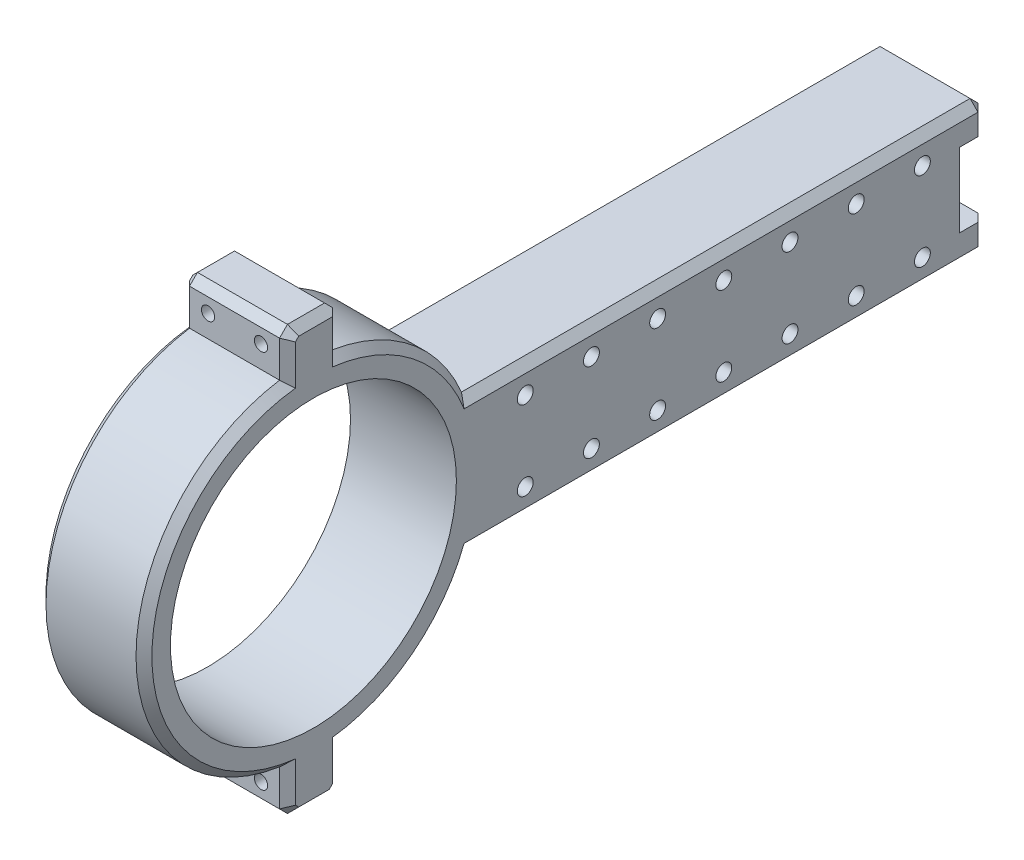
SolidWorks part; units mm, degrees
ref_plane "前视基准面" through (0, 0, 0) normal (0, 0, 1) x (1, 0, 0)
ref_plane "上视基准面" through (0, 0, 0) normal (0, 1, 0) x (1, 0, 0)
ref_plane "右视基准面" through (0, 0, 0) normal (1, 0, 0) x (0, 0, -1)
sketch "草图2" plane through (0, 0, 0) normal (1, 0, 0) x (0, 0, -1)
  circle A0 centre (0, 0) radius 32
  dimension "D1" = 64
extrude "凸台-拉伸1" add sketch "草图2" along normal blind 20
sketch "草图3" plane through (20, 0, 0) normal (1, 0, 0) x (0, 0, -1)
  circle A0 centre (0, 0) radius 27
  dimension "D1" = 54
extrude "切除-拉伸1" cut sketch "草图3" against normal through all
sketch "草图4" plane through (20, 0, 0) normal (1, 0, 0) x (0, 0, -1)
  line L1 (23.9322, 12.5) -> (122, 12.5)
  line L2 (23.9322, 12.5) -> (23.9322, -12.5)
  line L3 (23.9322, -12.5) -> (122, -12.5)
  line L4 (122, 12.5) -> (122, -12.5)
  line L5 (23.9322, 12.5) -> (122, -12.5) construction
  line L6 (23.9322, -12.5) -> (122, 12.5) construction
  circle A0 centre (0, 0) radius 27 construction
  circle A1 centre (0, 0) radius 32 construction
  point P0 (72.9661, 0)
  dimension "D1" = 122
  dimension "D2" = 25
extrude "凸台-拉伸2" add sketch "草图4" against normal blind 20
sketch "草图5" plane through (20, 0, 0) normal (1, 0, 0) x (0, 0, -1)
  circle A0 centre (0, 0) radius 27
  dimension "D1" = 54
extrude "切除-拉伸2" cut sketch "草图5" against normal through all
sketch "草图8" plane through (20, 0, 0) normal (1, 0, 0) x (0, 0, -1)
  line L0 (-32, 0) -> (122, 0) construction
  line L1 (5.0998, 26.5516) -> (-4.9002, 26.5516)
  line L2 (5.0998, 26.5516) -> (5.0998, 40)
  line L3 (5.0998, 40) -> (-4.9002, 40)
  line L4 (-4.9002, 26.5516) -> (-4.9002, 40)
  line L5 (5.0998, 26.5516) -> (-4.9002, 40) construction
  line L6 (5.0998, 40) -> (-4.9002, 26.5516) construction
  line L7 (122, -12.5) -> (122, 12.5) construction
  line L8 (5.0998, -40) -> (-4.9002, -40)
  line L9 (-4.9002, -26.5516) -> (-4.9002, -40)
  line L10 (5.0998, -26.5516) -> (-4.9002, -26.5516)
  line L11 (5.0998, -26.5516) -> (5.0998, -40)
  line L12 (0.0998, 50.6797) -> (0.0998, -34.5244) construction
  circle A0 centre (0, 0) radius 27 construction
  arc A1 (29.4576, 12.5) -> (29.4576, -12.5) centre (0, 0) ccw construction
  arc A2 (29.4576, 12.5) -> (29.4576, -12.5) centre (0, 0) ccw construction
  point P0 (0.0998, 33.2758)
  dimension "D1" = 10
  dimension "D2" = 40
extrude "凸台-拉伸4" add sketch "草图8" against normal up to surface (20 mm away) up to face at (0, 0, -60.3644)
sketch "草图9" plane through (0, 0, 4.9002) normal (0, 0, 1) x (1, 0, 0)
  line L0 (0, 35.8113) -> (20, 35.8113) construction
  line L1 (0, 40) -> (0, 31.6226) construction
  line L2 (20, 40) -> (20, 31.6226) construction
  line L3 (10, 40) -> (10, 31.6226) construction
  line L4 (0, 40) -> (20, 40) construction
  line L5 (20, 31.6226) -> (0, 31.6226) construction
  line L6 (0, 0) -> (28.5789, 0) construction
  circle A0 centre (5, 35.8113) radius 1.25
  circle A1 centre (15, 35.8113) radius 1.25
  circle A2 centre (15, -35.8113) radius 1.25
  circle A3 centre (5, -35.8113) radius 1.25
  dimension "D1" = 2.5
  dimension "D2" = 2.5
  dimension "D3" = 5
extrude "切除-拉伸4" cut sketch "草图9" against normal up to next
sketch "草图10" plane through (20, 0, 0) normal (1, 0, 0) x (0, 0, -1)
  circle A0 centre (0, 0) radius 27
  dimension "D1" = 54
extrude "切除-拉伸5" cut sketch "草图10" against normal through all
chamfer "倒角2" distance 1.5 angle 45 4 edges at (10, -40, 4.9002) (10, -40, -5.0998) (10, 40, -5.0998) (10, 40, 4.9002)
chamfer "倒角3" distance 1.5 angle 45 25 edges at (0, -25.1859, -19.74) (0, -35.0455, -5.0998) (0, -39.25, -4.3498) (0, -40, -0.0998) (0, -39.25, 4.1502) (0, -35.0613, 4.9002) (0, 25.1859, -19.74) (0, 35.0455, -5.0998) (0, 39.25, -4.3498) (0, 40, -0.0998) (0, 39.25, 4.1502) (0, 35.0613, 4.9002) (0, 0, 32) (20, 35.0455, -5.0998) (20, 25.1859, -19.74) (20, -25.1859, -19.74) (20, -35.0455, -5.0998) (20, -39.25, -4.3498) (20, -40, -0.0998) (20, -39.25, 4.1502) (20, -35.0613, 4.9002) (20, 40, -0.0998) (20, 39.25, 4.1502) (20, 35.0613, 4.9002) (20, 0, 32)
sketch "草图17" plane through (0, 0, -122) normal (0, 0, -1) x (-1, 0, 0)
  line L0 (0, 12.5) -> (-20, 12.5) construction
  line L1 (0, 7) -> (-20, 7)
  line L2 (0, 7) -> (0, 12.5)
  line L3 (0, 12.5) -> (-20, 12.5)
  line L4 (-20, 7) -> (-20, 12.5)
  line L5 (0, 7) -> (-20, 12.5) construction
  line L6 (0, 12.5) -> (-20, 7) construction
  line L7 (-20, -12.5) -> (-20, 12.5) construction
  line L8 (0, -12.5) -> (0, 12.5) construction
  line L9 (-20, 0) -> (0, 0) construction
  line L10 (0, -12.5) -> (-20, -12.5)
  line L11 (-20, -7) -> (-20, -12.5)
  line L12 (0, -7) -> (-20, -7)
  line L13 (0, -7) -> (0, -12.5)
  point P0 (-10, 9.75)
  dimension "D1" = 14
extrude "凸台-拉伸5" add sketch "草图17" along normal blind 5
sketch "草图18" plane through (0, 0, -122) normal (0, 0, -1) x (-1, 0, 0)
  line L0 (-20, 0) -> (0, 0) construction
  line L1 (-20, -7) -> (-20, 7) construction
  line L2 (0, -7) -> (0, 7) construction
  line L4 (-20, 7) -> (0, 7) construction
  line L5 (-10, 7) -> (-10, -7) construction
  line L6 (0, -7) -> (-20, -7) construction
  circle A0 centre (-16.25, 0) radius 1.25
  circle A1 centre (-3.75, 0) radius 1.25
  point P16 (0, 0)
  dimension "D1" = 2.5
  dimension "D2" = 2.5
  dimension "D3" = 12.5
extrude "切除-拉伸11" cut sketch "草图18" against normal blind 20
sketch "草图19" plane through (20, 0, 0) normal (1, 0, 0) x (0, 0, -1)
  line L0 (122, 0) -> (27, 0) construction
  line L1 (122, -7) -> (122, 7) construction
  circle A0 centre (0, 0) radius 27 construction
  circle A1 centre (40, 7.5) radius 1.5
  circle A2 centre (40, -7.5) radius 1.5
  circle A3 centre (52.5, 7.5) radius 1.5
  circle A4 centre (52.5, -7.5) radius 1.5
  circle A5 centre (65, 7.5) radius 1.5
  circle A6 centre (65, -7.5) radius 1.5
  circle A7 centre (77.5, 7.5) radius 1.5
  circle A8 centre (77.5, -7.5) radius 1.5
  circle A9 centre (90, 7.5) radius 1.5
  circle A10 centre (90, -7.5) radius 1.5
  circle A11 centre (102.5, 7.5) radius 1.5
  circle A12 centre (102.5, -7.5) radius 1.5
  circle A13 centre (115, 7.5) radius 1.5
  circle A14 centre (115, -7.5) radius 1.5
  dimension "D1" = 3
  dimension "D2" = 3
  dimension "D3" = 15
  dimension "D4" = 40
  dimension "D5" = 7
extrude "切除-拉伸12" cut sketch "草图19" against normal through all
chamfer "倒角4" distance 1.5 angle 45 10 edges at (20, -9.75, -127) (0, -9.75, -127) (10, -12.5, -127) (20, -12.5, -77.4104) (0, 9.75, -127) (20, 9.75, -127) (10, 12.5, -127) (20, 12.5, -77.4104) (0, -12.5, -77.4104) (0, 12.5, -77.4104)
sketch "草图11" plane through (0, 0, 0) normal (0, 0, 1) x (1, 0, 0)
  line L1 (60.6516, -49.0819) -> (-27.9407, -49.0819)
  line L2 (60.6516, -49.0819) -> (60.6516, 47.2432)
  line L3 (60.6516, 47.2432) -> (-27.9407, 47.2432)
  line L4 (-27.9407, -49.0819) -> (-27.9407, 47.2432)
  line L5 (60.6516, -49.0819) -> (-27.9407, 47.2432) construction
  line L6 (60.6516, 47.2432) -> (-27.9407, -49.0819) construction
  point P0 (16.3554, -0.9194)
extrude "切除-拉伸9" [suppressed] cut sketch "草图11" against normal through all
sketch "草图16" [suppressed] plane through (0, 0, 0) normal (0, 0, -1) x (-1, 0, 0)
  circle A0 centre (-15, 35.8113) radius 1.5
  circle A1 centre (-5, 35.8113) radius 1.5
  circle A2 centre (-5, -35.8113) radius 1.5
  circle A3 centre (-15, -35.8113) radius 1.5
  point P19 (0, 0)
  dimension "D1" = 3
extrude "切除-拉伸10" [suppressed] cut sketch "草图16" against normal up to next
